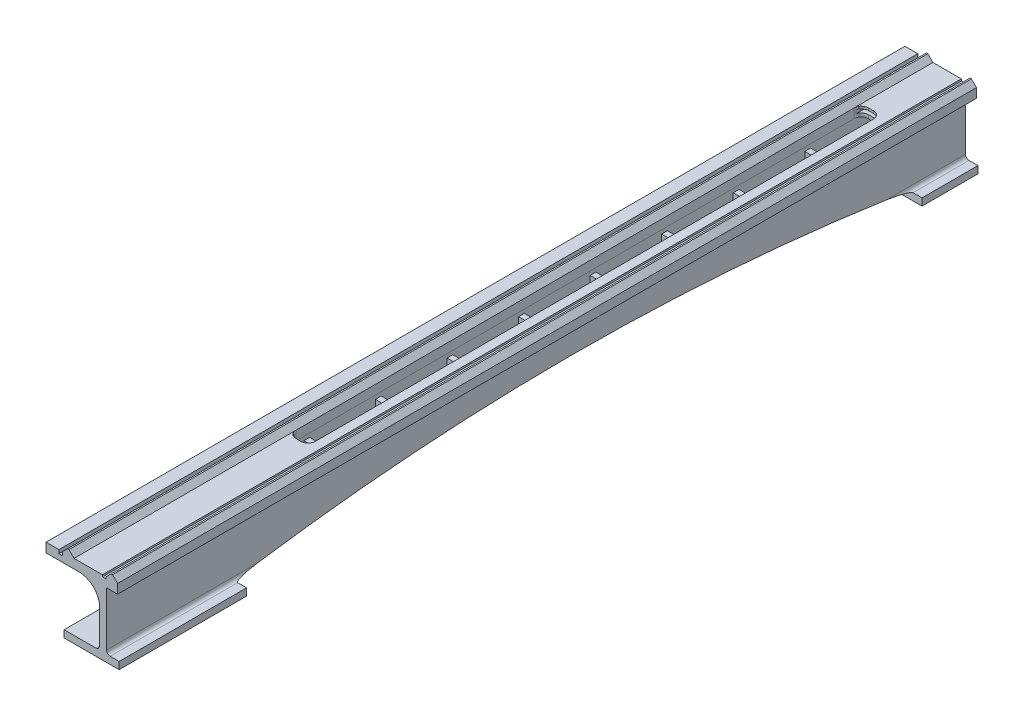
SolidWorks part; units mm, degrees
ref_plane "Front Plane" through (0, 0, 0) normal (0, 0, 1) x (1, 0, 0)
ref_plane "Top Plane" through (0, 0, 0) normal (0, 1, 0) x (1, 0, 0)
ref_plane "Right Plane" through (0, 0, 0) normal (1, 0, 0) x (0, 0, -1)
sketch "Sketch1" plane through (0, 0, 0) normal (0, 0, 1) x (1, 0, 0)
  line L0 (-33.3128, 35.4652) -> (-40.3839, 42.5363)
  line L2 (-133.3128, 35.4652) -> (-133.3128, 22.5363)
  line L4 (-33.3128, 35.4652) -> (-33.3128, 22.5363)
  line L5 (-40.3839, 42.5363) -> (-42.3839, 42.5363)
  line L6 (-42.3839, 42.5363) -> (-49.455, 35.4652)
  line L7 (-49.455, 35.4652) -> (-49.455, 32.891)
  line L8 (-49.455, 32.891) -> (-54.455, 32.891)
  line L9 (-54.455, 32.891) -> (-54.455, 35.4652)
  line L10 (-54.455, 35.4652) -> (-94.1707, 35.4652)
  line L14 (-94.1707, 35.4652) -> (-101.2418, 42.5363)
  line L15 (-101.2418, 42.5363) -> (-103.2418, 42.5363)
  line L16 (-103.2418, 42.5363) -> (-110.3128, 35.4652)
  line L17 (-110.3128, 35.4652) -> (-110.3128, 30.4818)
  line L18 (-110.3128, 30.4818) -> (-115.3128, 30.4818)
  line L19 (-115.3128, 30.4818) -> (-115.3128, 35.4652)
  line L20 (-115.3128, 35.4652) -> (-133.3128, 35.4652)
  line L21 (-133.3128, 22.5363) -> (-87.3496, 22.5363)
  line L22 (-33.3128, 22.5363) -> (-48.7011, 22.5363)
  line L23 (-48.7011, 22.5363) -> (-48.7011, -52.7938)
  line L24 (-43.7011, -57.7938) -> (-31.1954, -57.7938)
  line L25 (-31.1954, -57.7938) -> (-31.1954, -67.7938)
  line L26 (-31.1954, -67.7938) -> (-108.01, -67.7938)
  line L27 (-108.01, -67.7938) -> (-108.01, -57.7938)
  line L28 (-108.01, -57.7938) -> (-63.7011, -57.7938)
  line L29 (-58.7011, -52.7938) -> (-58.7011, -0.8365)
  arc A0 (-87.3496, 22.5363) -> (-58.7011, -0.8365) centre (-87.3496, -6.7076) cw
  arc A1 (-48.7011, -52.7938) -> (-43.7011, -57.7938) centre (-43.7011, -52.7938) ccw
  arc A2 (-63.7011, -57.7938) -> (-58.7011, -52.7938) centre (-63.7011, -52.7938) ccw
  point P12 (-93.8283, 35.4651)
  point P30 (-48.7011, -57.7938)
  dimension "D17" = 5
  dimension "D1" = 100
  dimension "D2" = 10
  dimension "D3" = 2
  dimension "D4" = 5
  dimension "D5" = 18
  dimension "D6" = 5
  dimension "D7" = 20
  dimension "D8" = 135
  dimension "D9" = 10
  dimension "D10" = 10
  dimension "D11" = 2
  dimension "D12" = 10
  dimension "D13" = 10
  dimension "D14" = 58.8579
  dimension "D15" = 10
  dimension "D16" = 20
extrude "Boss-Extrude1" add sketch "Sketch1" along normal blind 1200
sketch "Sketch2" plane through (0, 20.7647, 0) normal (0, 1, 0) x (1, 0, 0)
  line L0 (-94.1707, -1200) -> (-94.1707, 0) construction
  line L1 (-84.1707, -100) -> (-77.1707, -100)
  line L2 (-94.1707, -110) -> (-94.1707, -890)
  line L3 (-84.1707, -900) -> (-77.1707, -900)
  line L4 (-67.1707, -110) -> (-67.1707, -890)
  line L5 (-67.1707, -1200) -> (-67.1707, 0) construction
  line L6 (-54.455, 0) -> (-94.1707, 0) construction
  arc A0 (-94.1707, -890) -> (-84.1707, -900) centre (-84.1707, -890) ccw
  arc A1 (-77.1707, -900) -> (-67.1707, -890) centre (-77.1707, -890) ccw
  arc A2 (-77.1707, -100) -> (-67.1707, -110) centre (-77.1707, -110) cw
  arc A3 (-84.1707, -100) -> (-94.1707, -110) centre (-84.1707, -110) ccw
  point P12 (-67.1707, -900)
  point P15 (-67.1707, -100)
  point P18 (-94.1707, -100)
  dimension "D2" = 10
  dimension "D1" = 800
  dimension "D3" = 100
extrude "Cut-Extrude1" cut sketch "Sketch2" along normal blind 800
sketch "Sketch3" plane through (0, 0, 1200) normal (0, 0, 1) x (1, 0, 0)
  line L1 (-61.1129, 27.3205) -> (-93.9675, 27.3205)
  line L2 (-61.1129, 27.3205) -> (-61.1129, 32.1773)
  line L3 (-61.1129, 32.1773) -> (-93.9675, 32.1773)
  line L4 (-93.9675, 27.3205) -> (-93.9675, 32.1773)
extrude "Cut-Extrude2" cut sketch "Sketch3" against normal blind 900 from offset 300 offset against normal yes
sketch "Sketch5" plane through (0, 0, 0) normal (0, 0, -1) x (-1, 0, 0)
  line L1 (101.3003, -59.4347) -> (94.9198, -59.4347)
  line L2 (101.3003, -59.4347) -> (101.3003, 27.7967)
  line L3 (101.3003, 27.7967) -> (94.9198, 27.7967)
  line L4 (94.9198, -59.4347) -> (94.9198, 27.7967)
extrude "Boss-Extrude2" add sketch "Sketch5" against normal blind 1100
sketch "Sketch6" plane through (-101.3003, 0, 0) normal (-1, 0, 0) x (0, 0, 1)
  line L1 (70.1556, 16.5847) -> (78.2516, 16.5847)
  line L2 (70.1556, 16.5847) -> (70.1556, -47.4448)
  line L3 (70.1556, -47.4448) -> (78.2516, -47.4448)
  line L4 (78.2516, 16.5847) -> (78.2516, -47.4448)
extrude "Boss-Extrude3" add sketch "Sketch6" against normal blind 50
pattern_linear "LPattern1" count 10 spacing 100 along (0, 0, 1) of "Boss-Extrude3"
sketch "Sketch4" plane through (-33.3128, 0, 0) normal (1, 0, 0) x (0, 0, -1)
  line L0 (-1021.7946, -57.7938) -> (-1021.7946, -67.7938)
  line L1 (-1200, -57.7938) -> (0, -57.7938) construction
  line L2 (-1200, -67.7938) -> (0, -67.7938) construction
  line L3 (-1021.7946, -67.7938) -> (-1021.7946, -177.9566)
  line L4 (-1021.7946, -177.9566) -> (-78.2516, -177.9566)
  line L5 (-78.2516, -177.9566) -> (-78.2516, -57.7938)
  arc A0 (-1021.7946, -57.7938) -> (-78.2516, -57.7938) centre (-550.0231, -3038.7634) cw
extrude "Cut-Extrude3" cut sketch "Sketch4" against normal blind 100 and the other way blind 10
